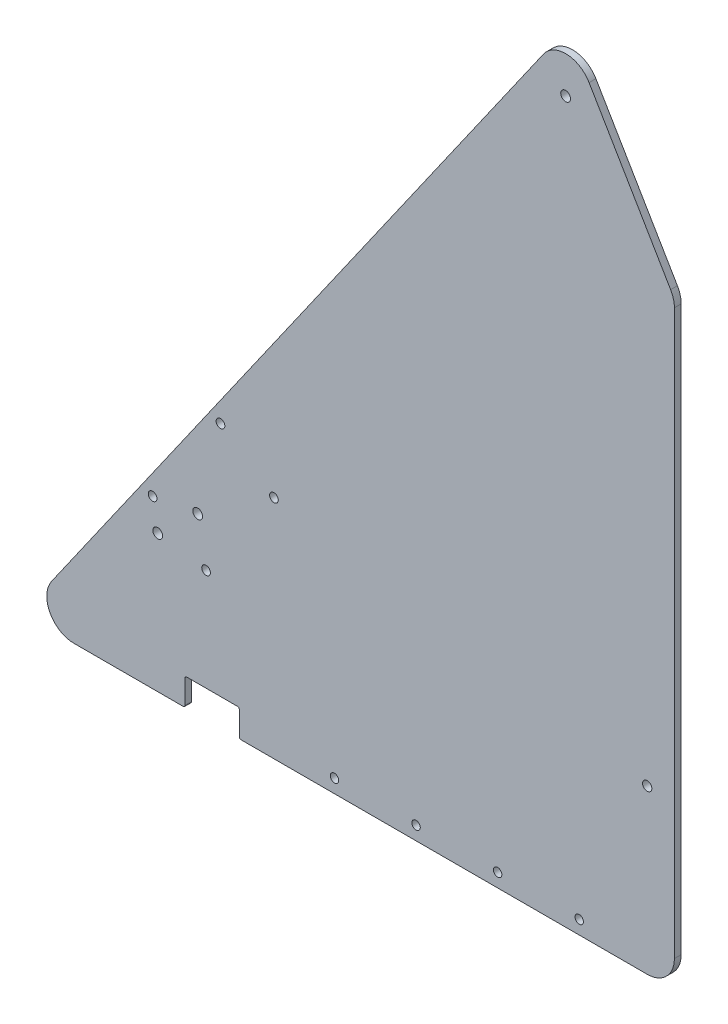
SolidWorks part; units mm, degrees
other "Markup1"
sketch "Sketch5"
ref_plane "Front Plane" through (0, 0, 0) normal (0, 0, 1) x (1, 0, 0)
ref_plane "Top Plane" through (0, 0, 0) normal (0, 1, 0) x (1, 0, 0)
ref_plane "Right Plane" through (0, 0, 0) normal (1, 0, 0) x (0, 0, -1)
sketch "Sketch1" plane through (0, 0, 0) normal (0, 0, 1) x (1, 0, 0)
  line L0 (0, 0) -> (76.2, 0)
  line L1 (304.8, 0) -> (304.8, 279.4)
  line L2 (254.9547, 364.1131) -> (0, 0)
  line L3 (304.8, 279.4) -> (254.9547, 364.1131)
  line L4 (76.2, 0) -> (76.2, 12.7)
  line L5 (76.2, 12.7) -> (101.6, 12.7)
  line L6 (101.6, 12.7) -> (101.6, 0)
  line L7 (101.6, 0) -> (304.8, 0)
  dimension "D7" = 12.7
  dimension "D1" = 304.8
  dimension "D2" = 279.4
  dimension "D3" = 55
  dimension "D4" = 444.5
  dimension "D5" = 76.2
  dimension "D6" = 25.4
extrude "Boss-Extrude1" add sketch "Sketch1" along normal blind 3.175
sketch "Sketch2" plane through (0, 0, 3.175) normal (0, 0, 1) x (1, 0, 0)
  line L0 (254.9547, 364.1131) -> (0, 0) construction
  line L1 (101.6, 0) -> (304.8, 0) construction
  circle A0 centre (63.5, 64.1173) radius 2.286
  circle A1 centre (254, 336.1795) radius 2.286
  circle A2 centre (82.1575, 81.3527) radius 2.286
  circle A3 centre (292.1, 76.2) radius 2.159 construction
  circle A4 centre (292.1, 76.2) radius 2.159
  circle A5 centre (184.15, 6.35) radius 1.9682
  circle A6 centre (222.25, 6.35) radius 1.9682
  circle A7 centre (260.35, 6.35) radius 1.9682
  circle A28 centre (92.8016, 123.1242) radius 2.032
  circle A29 centre (92.8016, 123.1242) radius 2.032
  circle A34 centre (61.1144, 77.8702) radius 2.032
  circle A35 centre (61.1144, 77.8702) radius 2.032
  circle A37 centre (86.0822, 60.3876) radius 2.032
  circle A38 centre (86.0822, 60.3876) radius 2.032
  circle A39 centre (117.7694, 105.6416) radius 2.032
  circle A40 centre (117.7694, 105.6416) radius 2.032
  circle A41 centre (146.05, 6.35) radius 1.9682
  dimension "D3" = 4.572
  dimension "D5" = 4.572
  dimension "D9" = 4.572
  dimension "D14" = 3.9364
  dimension "D1" = 63.5
  dimension "D2" = 15.24
  dimension "D4" = 254
  dimension "D6" = 15.24
  dimension "D7" = 25.4
  dimension "D8" = 20.6375
  dimension "D15" = 146.05
  dimension "D16" = 6.35
  dimension "D10" = 0.127
  dimension "D12" = 0.127
  dimension "D13" = 0.127
  dimension "D11" = 0.127
  dimension "D17" = 4
extrude "Cut-Extrude1" cut sketch "Sketch2" against normal through all
fillet "Fillet1" radius 12.7 4 edges at (0, 0, 1.5875) (304.8, 0, 1.5875) (304.8, 279.4, 1.5875) (254.9547, 364.1131, 1.5875)
fillet "Fillet2" radius 0.7937 4 edges at (101.6, 0, 1.5875) (101.6, 12.7, 1.5875) (76.2, 0, 1.5875) (76.2, 12.7, 1.5875)
equation "\"D6@Sketch2\"=\"D2@Sketch2\""
